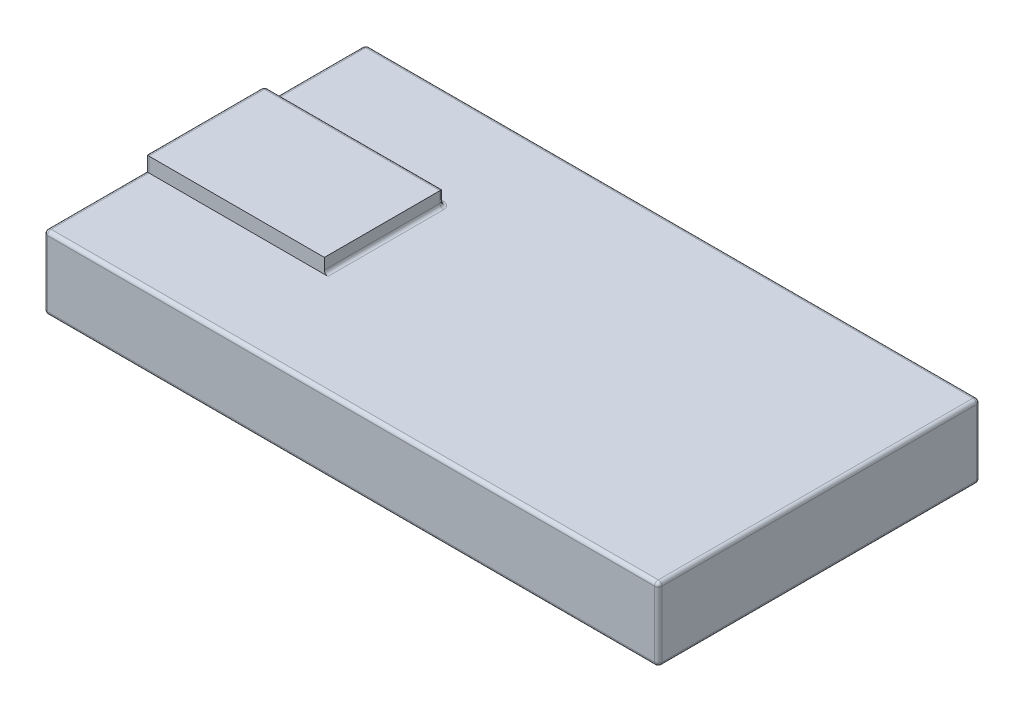
SolidWorks part; units mm, degrees
ref_plane "前视基准面" through (0, 0, 0) normal (0, 0, 1) x (1, 0, 0)
ref_plane "上视基准面" through (0, 0, 0) normal (0, 1, 0) x (1, 0, 0)
ref_plane "右视基准面" through (0, 0, 0) normal (1, 0, 0) x (0, 0, -1)
sketch "草图1" plane through (0, 0, 0) normal (0, 1, 0) x (1, 0, 0)
  line L1 (-42, 22) -> (42, 22)
  line L2 (-42, 22) -> (-42, -22)
  line L3 (-42, -22) -> (42, -22)
  line L4 (42, 22) -> (42, -22)
  line L5 (0, -22) -> (0, 22) construction
  line L6 (-42, 0) -> (42, 0) construction
  point P0 (0, 0)
  dimension "D1" = 44
  dimension "D2" = 84
extrude "凸台-拉伸1" add sketch "草图1" along normal blind 10
sketch "草图3" plane through (0, 10, 0) normal (0, 1, 0) x (1, 0, 0)
  line L0 (-42, -8.15) -> (-17.5, -8.15)
  line L1 (-42, 22) -> (-42, -22) construction
  line L2 (-17.5, -8.15) -> (-17.5, 8.15)
  line L3 (-17.5, 8.15) -> (-42, 8.15)
  line L4 (-42, 8.15) -> (-42, -8.15)
  line L5 (-42, -22) -> (42, -22) construction
  dimension "D1" = 16.3
  dimension "D2" = 13.85
  dimension "D3" = 24.5
extrude "凸台-拉伸2" add sketch "草图3" along normal blind 2
fillet "圆角1" radius 0.5 1 edges at (42, 10, 0)
fillet "圆角2" radius 0.5 4 edges at (42, 4.75, 22) (41.8536, 9.8536, 22) (-0.25, 10, 22) (0, 0, 22)
fillet "圆角3" radius 0.5 20 edges at (-17.5, 10, 0) (-0.25, 10, -22) (41.8536, 9.8536, -22) (41.8536, 0.1464, 21.8536) (-42, 0, -0.25) (-42, 0.1464, 21.8536) (-42, 5, 22) (-42, 9.8536, 21.8536) (42, 4.75, -22) (42, 0, -0.25) (-17.5, 11, -8.15) (-29.75, 12, -8.15) (-42, 11, -8.15) (-29.75, 10, -8.15) (-42, 10, 14.825) (-42, 11, 8.15) (-42, 12, 0) (-42, 10, -15.075) (-42, 5, -22) (0, 0, -22)
